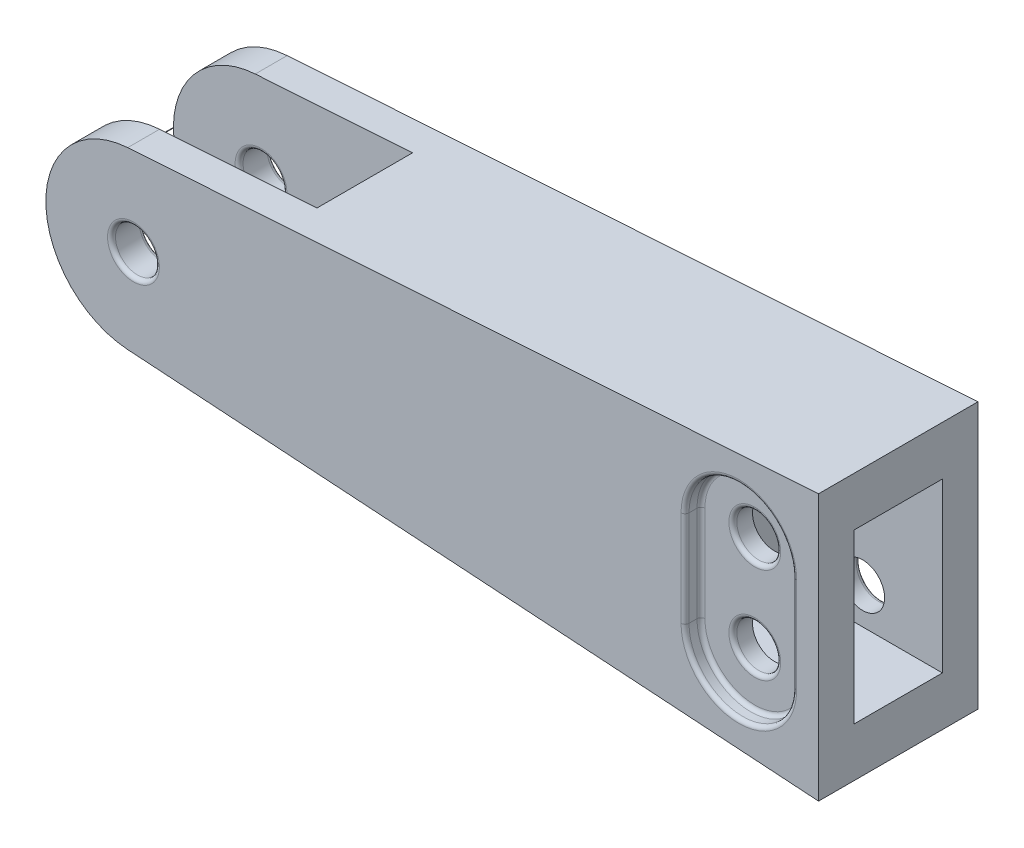
SolidWorks part; units mm, degrees
ref_plane "Front Plane" through (0, 0, 0) normal (0, 0, 1) x (1, 0, 0)
ref_plane "Top Plane" through (0, 0, 0) normal (0, 1, 0) x (1, 0, 0)
ref_plane "Right Plane" through (0, 0, 0) normal (1, 0, 0) x (0, 0, -1)
sketch "Sketch1" plane through (0, 0, 0) normal (0, 0, 1) x (1, 0, 0)
  line L1 (43.0973, 0) -> (50043.0973, 0) construction
  line L2 (0, 21.9801) -> (0, 50021.9801) construction
  line L5 (-147.5823, 10.9687) -> (-60.9236, 16.6957)
  line L6 (-60.9236, -16.6957) -> (-17.5178, -19.5642) construction
  line L7 (-60.9236, 16.6957) -> (-60.9236, -16.6957) construction
  line L8 (-60.9236, 16.6957) -> (-60.9236, -16.6957)
  line L9 (-147.5823, -10.9687) -> (-60.9236, -16.6957)
  arc A1 (-147.5823, 10.9687) -> (-147.5823, -10.9687) centre (-146.8574, 0) ccw
  point P9 (0, 0)
  dimension "D1" = 146.8574
extrude "Boss-Extrude1" add sketch "Sketch1" along normal up to surface (20 mm away) contours A1 region at (-104.6886, 0, 0)
sketch "Sketch2" plane through (-60.9236, 0, 0) normal (1, 0, 0) x (0, 0, -1)
  line L0 (-10, -20) -> (-10, 20) construction
  line L4 (-15.535, -10.535) -> (-4.465, -10.535)
  line L5 (-15.535, -10.535) -> (-15.535, 10.535)
  line L6 (-15.535, 10.535) -> (-4.465, 10.535)
  line L16 (-20, -20) -> (0, -20) construction
  line L17 (-20, 20) -> (-20, -20) construction
  line L18 (0, 20) -> (-20, 20) construction
  line L19 (0, -20) -> (0, 20) construction
  line L20 (-4.465, -10.535) -> (-4.465, 10.535)
  line L21 (-15.535, -10.535) -> (-4.465, 10.535) construction
  line L22 (-15.535, 10.535) -> (-4.465, -10.535) construction
  line L23 (0, 0) -> (-20, 0) construction
  point P2 (-10, 0)
  point P15 (-10, 0)
  dimension "D2" = 11.07
  dimension "D3" = 21.07
  dimension "D1" = 40
  dimension "D4" = 20
  dimension "D5" = 10
extrude "Cut-Extrude1" cut sketch "Sketch2" against normal blind 20
sketch "Sketch4" plane through (0, 0, 0) normal (0, 1, 0) x (1, 0, 0)
  line L0 (-60.9236, -20) -> (-147.5823, -20) construction
  line L5 (-157.85, 0) -> (-157.85, -20) construction
  line L6 (-157.85, -4) -> (-127.85, -4)
  line L7 (-157.85, -4) -> (-157.85, -16)
  line L10 (-157.85, -16) -> (-127.85, -16)
  line L15 (-127.85, -4) -> (-127.85, -16)
  line L16 (-157.85, -4) -> (-127.85, -16) construction
  line L17 (-157.85, -16) -> (-127.85, -4) construction
  line L18 (-147.5823, 0) -> (-157.8501, 0) construction
  point P4 (-142.85, -10)
  dimension "D1" = 4
  dimension "D2" = 4
  dimension "D3" = 30
extrude "Cut-Extrude2" cut sketch "Sketch4" against normal through all both and the other way through all
sketch "Sketch5" plane through (0, 0, 0) normal (0, 0, -1) x (-1, 0, 0)
  circle A0 centre (146.8574, 0) radius 2.75
  dimension "D1" = 5.5
extrude "Cut-Extrude3" cut sketch "Sketch5" against normal through all
sketch "Sketch6" plane through (0, 0, 0) normal (0, 0, -1) x (-1, 0, 0)
  line L1 (0, 0) -> (50000, 0) construction
  line L2 (60.9236, 16.6957) -> (60.9236, -16.6957) construction
  circle A0 centre (70.9236, -6) radius 2.75
  circle A1 centre (70.9236, 6) radius 2.75
  dimension "D1" = 5.5
  dimension "D2" = 10
  dimension "D3" = 6
extrude "Cut-Extrude4" cut sketch "Sketch6" against normal through all
sketch "Sketch8" plane through (0, 0, 0) normal (0, 0, -1) x (-1, 0, 0)
  line L0 (64.1736, 6) -> (64.1736, -6)
  line L2 (77.6736, 6) -> (77.6736, -6)
  circle A0 centre (70.9236, -6) radius 2.75 construction
  circle A1 centre (70.9236, 6) radius 2.75 construction
  circle A2 centre (70.9236, -6) radius 2.75 construction
  circle A3 centre (70.9236, 6) radius 2.75 construction
  arc A4 (64.1736, -6) -> (77.6736, -6) centre (70.9236, -6) ccw
  arc A5 (77.6736, 6) -> (64.1736, 6) centre (70.9236, 6) ccw
  circle A6 centre (70.9236, 6) radius 6.75 construction
  circle A7 centre (70.9236, -6) radius 6.75 construction
  dimension "D1" = 4
extrude "Cut-Extrude5" cut sketch "Sketch8" against normal blind 2
ref_plane "Plane1" through (0, 0, 10) normal (0, 0, -1) x (-1, 0, 0)
mirror "Mirror1" about plane through (0, 0, 10) normal (0, 0, -1) of "Cut-Extrude5"
fillet "Fillet2" radius 0.5 24 edges at (-70.9236, -12.75, 2) (-64.1736, 0, 2) (-70.9236, 12.75, 2) (-70.9236, -12.75, 0) (-64.1736, 0, 0) (-70.9236, 12.75, 0) (-70.9236, -12.75, 18) (-64.1736, 0, 18) (-70.9236, 12.75, 18) (-70.9236, -12.75, 20) (-64.1736, 0, 20) (-70.9236, 12.75, 20) (-149.6074, 0, 4) (-149.6074, 0, 0) (-144.1074, 0, 16) (-149.6074, 0, 20) (-68.1736, -6, 18) (-68.1736, 6, 18) (-73.6736, -6, 2) (-73.6736, 6, 2) (-77.6736, 0, 18) (-77.6736, 0, 20) (-77.6736, 0, 2) (-77.6736, 0, 0)
